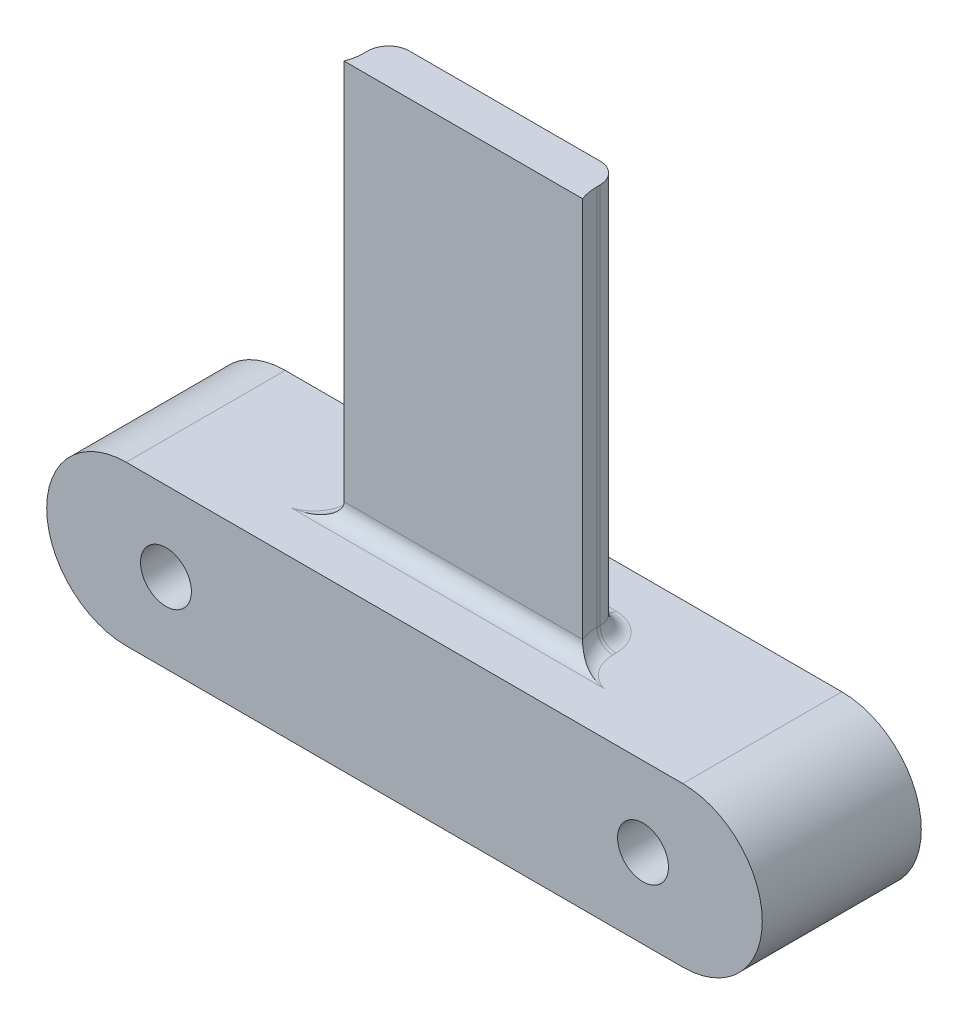
SolidWorks part; units mm, degrees
ref_plane "Спереди" through (0, 0, 0) normal (0, 0, 1) x (1, 0, 0)
ref_plane "Сверху" through (0, 0, 0) normal (0, 1, 0) x (1, 0, 0)
ref_plane "Справа" through (0, 0, 0) normal (1, 0, 0) x (0, 0, -1)
sketch "Эскиз1" plane through (0, 0, 0) normal (0, 0, 1) x (1, 0, 0)
  line L0 (-22.5, 0) -> (22.5, 0) construction
  line L1 (-22.5, -5) -> (22.5, -5)
  line L2 (-22.5, -5) -> (-22.5, 5)
  line L3 (-22.5, 5) -> (22.5, 5)
  line L4 (22.5, -5) -> (22.5, 5)
  line L5 (-22.5, -5) -> (22.5, 5) construction
  line L6 (-22.5, 5) -> (22.5, -5) construction
  line L7 (0, 5) -> (0, -5) construction
  circle A0 centre (-15, 0) radius 1.6
  circle A1 centre (15, 0) radius 1.6
  point P0 (0, 0)
  dimension "D1" = 3.2
  dimension "D2" = 15
  dimension "D3" = 45
  dimension "D4" = 10
extrude "Бобышка-Вытянуть1" add sketch "Эскиз1" along normal mid plane 10
fillet "Скругление1" 2 edges at (-22.5, 5, 0) (-22.5, -5, 0) type full round first side face at (0, 5, 0) second side face at (0, -5, 0) middle face at (-22.5, 0, 0)
fillet "Скругление2" 2 edges at (22.5, 5, 0) (22.5, -5, 0) type full round first side face at (2.5, 5, 0) second side face at (2.5, -5, 0) middle face at (22.5, 0, 0)
sketch "Эскиз2" plane through (0, 5, 0) normal (0, 1, 0) x (1, 0, 0)
  line L0 (0, 5) -> (0, -5) construction
  line L1 (17.5, 5) -> (-17.5, 5) construction
  line L2 (17.5, -5) -> (-17.5, -5) construction
  line L3 (-17.5, 0) -> (17.5, 0) construction
  line L4 (-17.5, 5) -> (-17.5, -5) construction
  line L5 (17.5, -5) -> (17.5, 5) construction
  line L6 (-6, 2) -> (6, 2)
  line L7 (-8, 0) -> (-8, -0.2)
  line L8 (8, 0) -> (8, -0.2)
  line L10 (-8.7651, -2) -> (8.7651, -2)
  line L11 (-6, 1.3) -> (6, 1.3)
  line L12 (7.3, 0) -> (7.3, -0.2)
  line L13 (-7.495, -1.3) -> (7.495, -1.3)
  line L14 (-7.3, 0) -> (-7.3, -0.2)
  arc A0 (-6, 2) -> (-8, 0) centre (-6, 0) ccw
  arc A1 (-8, -0.2) -> (-8.7651, -2) centre (-10.5, -0.2) cw
  arc A2 (6, 2) -> (8, 0) centre (6, 0) cw
  arc A3 (8, -0.2) -> (8.7651, -2) centre (10.5, -0.2) ccw
  arc A4 (6, 1.3) -> (7.3, 0) centre (6, 0) cw
  arc A5 (7.3, -0.2) -> (7.495, -1.3) centre (10.5, -0.2) ccw
  arc A6 (-7.3, -0.2) -> (-7.495, -1.3) centre (-10.5, -0.2) cw
  arc A7 (-6, 1.3) -> (-7.3, 0) centre (-6, 0) ccw
  point P26 (0, 2)
  dimension "D3" = 2.5
  dimension "D1" = 4
  dimension "D2" = 16
  dimension "D4" = 0.2
  dimension "D5" = 4
  dimension "D6" = 0.7
extrude "Бобышка-Вытянуть2" add sketch "Эскиз2" along normal blind 25 contours L11 A7 L14 A6 L13 A5 L12 A4 region at (0, 5, 0.0235)
fillet "Скругление8" radius 1 8 edges at (7.3491, 5, 0.7586) (7.3, 5, 0.1) (6.9192, 5, -0.9192) (0, 5, -1.3) (-6.9192, 5, -0.9192) (-7.3, 5, 0.1) (-7.3491, 5, 0.7586) (0, 5, 1.3)
sketch "Эскиз3" plane through (0, 30, 0) normal (0, 1, 0) x (1, 0, 0)
  line L0 (6, 0.3) -> (-6, 0.3)
  line L1 (-6.3, 0) -> (-6.3, -0.2)
  line L2 (-6.3012, -0.3) -> (6.3012, -0.3)
  line L3 (6.3, -0.2) -> (6.3, 0)
  line L4 (6, 1.3) -> (-6, 1.3)
  line L5 (-7.3, 0) -> (-7.3, -0.2)
  line L6 (-7.495, -1.3) -> (7.495, -1.3)
  line L7 (7.3, -0.2) -> (7.3, 0)
  line L8 (6, 1.3) -> (-6, 1.3)
  line L9 (-7.3, 0) -> (-7.3, -0.2)
  line L10 (-7.495, -1.3) -> (7.495, -1.3)
  line L11 (7.3, -0.2) -> (7.3, 0)
  arc A0 (-6, 0.3) -> (-6.3, 0) centre (-6, 0) ccw
  arc A1 (-6.3012, -0.3) -> (-6.3, -0.2) centre (-10.5, -0.2) ccw
  arc A2 (6.3, -0.2) -> (6.3012, -0.3) centre (10.5, -0.2) ccw
  arc A3 (6.3, 0) -> (6, 0.3) centre (6, 0) ccw
  arc A4 (-6, 1.3) -> (-7.3, 0) centre (-6, 0) ccw
  arc A5 (-7.495, -1.3) -> (-7.3, -0.2) centre (-10.5, -0.2) ccw
  arc A6 (7.3, -0.2) -> (7.495, -1.3) centre (10.5, -0.2) ccw
  arc A7 (7.3, 0) -> (6, 1.3) centre (6, 0) ccw
  arc A8 (-6, 1.3) -> (-7.3, 0) centre (-6, 0) ccw
  arc A9 (-7.495, -1.3) -> (-7.3, -0.2) centre (-10.5, -0.2) ccw
  arc A10 (7.3, -0.2) -> (7.495, -1.3) centre (10.5, -0.2) ccw
  arc A11 (7.3, 0) -> (6, 1.3) centre (6, 0) ccw
  dimension "D1" = 0
  dimension "D2" = 1
extrude "Вырез-Вытянуть1" cut sketch "Эскиз3" against normal blind 10 from offset 20 contours L3 A3 L0 A0 L1 A1 L2 A2 region at (0, 30, 0.0012) offset against normal yes
equation "\"DTailTube\"= 16mm'Диаметр трубки хвостового оперения"
equation "\"FusLenght\"= 700mm"
equation "\"DMotor\"= 35.2mm"
equation "\"MotorArm\"= 320mm"
equation "\"DFus\"= 150mm"
equation "\"DFusTube\"= 30mm'Диаметр трубки внутри фюзеляжа"
equation "\"FusTubeHeight\"= 40mm"
equation "\"FusCentralPartLenght\"= 410mm"
equation "\"FusNoseLenght\"= 150mm"
equation "\"WingOffset\"= 1mm'Расстояние от внутренней поверхности фюзеляжа до профиля крыла по вертикали"
equation "\"EllipseRatio\"= 0.95'Центральная часть фюзеляжа - эллипс. Этот параметр - отношение длин осей эллипса"
equation "\"FrameOffset\"= 0.6mm"
equation "\"DThreadedInsert\"= 3.6mm'Внешний диамер резьбовых втулок"
equation "\"CenterSectionLenght\"= 140mm'Длина центроплана"
equation "\"b\"= 1700mm'Размах"
equation "\"cwr\"= 236mm'Корневая хорда крыла"
equation "\"TR\"= 0.75'Сужение крыла"
equation "\"cwt\"= \"TR\" * \"cwr\"'Концевая хорда крыла"
equation "\"DWingMainSpar\"= 16mm'Диаметр главного лонжерона крыла"
equation "\"DWingSecondSpar\"= 8mm'Диаметр второго лонжерона крыла"
equation "\"WingSparsDistance\"= 80mm'Расстояния между отверстиями по лонжерон крыла"
equation "\"c\"= 210mm'САХ крыла"
equation "\"FusTubeLenght\"= \"FusLenght\"-50mm'Длина трубки фюзеляжа"
equation "\"bt\"=291mm'Высота лопатки хвоста"
equation "\"TailTubeLenght\"=730mm'Длина хвостовой балки"
equation "\"DStringer\"=6mm'Диаметр стрингеров"
equation "\"TailConnectorBaseLenght\"=20mm'Высота основания конектора хвоста"
equation "\"CargoHolderHoleDistance\"=30mm'Расстояние между крепежными отверстиями для держателя груза"
equation "\"D2@Эскиз1\"=\"CargoHolderHoleDistance\"/2"
equation "\"D3@Эскиз1\"=\"CargoHolderHoleDistance\"+15"
equation "\"ct\"=182mm'Корневая хорда хвоста"
equation "\"lambda_t\"=0.3'Доля хвоста, занатая рулем высоты"
equation "\"FuselageThickness\"=1.2mm'Толщина фюзеляжа"
equation "\"DTailSpar\"=6mm'Диаметр лонжерона хвостового оперения"
equation "\"TailSparDistance\"=40mm'Расстояние между лонжеронами хвостового оперения"
equation "\"CrossSectionWidth\"=15mm'Ширина кольцевой части шпангоута"
